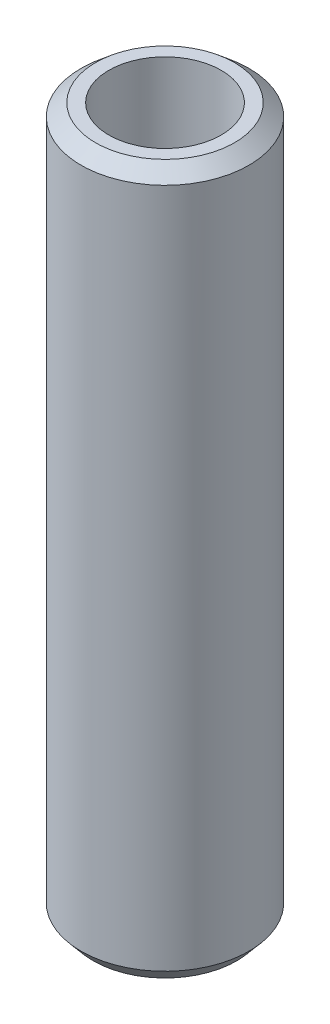
SolidWorks part; units mm, degrees
ref_plane "Front Plane" through (0, 0, 0) normal (0, 0, 1) x (1, 0, 0)
ref_plane "Top Plane" through (0, 0, 0) normal (0, 1, 0) x (1, 0, 0)
ref_plane "Right Plane" through (0, 0, 0) normal (1, 0, 0) x (0, 0, -1)
sketch "Sketch1" plane through (0, 0, 0) normal (0, 1, 0) x (1, 0, 0)
  circle A0 centre (0, 0) radius 20
  dimension "SHAFT_OD" = 40
extrude "Boss-Extrude1" add sketch "Sketch1" along normal blind 168.4799
sketch "Sketch2" plane through (0, 0, 0) normal (0, 1, 0) x (1, 0, 0)
  circle A0 centre (0, 0) radius 13.3769
  dimension "BORE_D" = 26.7539
extrude "Cut-Extrude1" cut sketch "Sketch2" along normal through all
chamfer "Chamfer1" distance 2.9121 angle 49.84 2 edges at (0, 168.4799, 20) (0, 0, 20) first distance on face at (0, 168.4799, 20) first distance on face at (0, 0, 13.3769)
